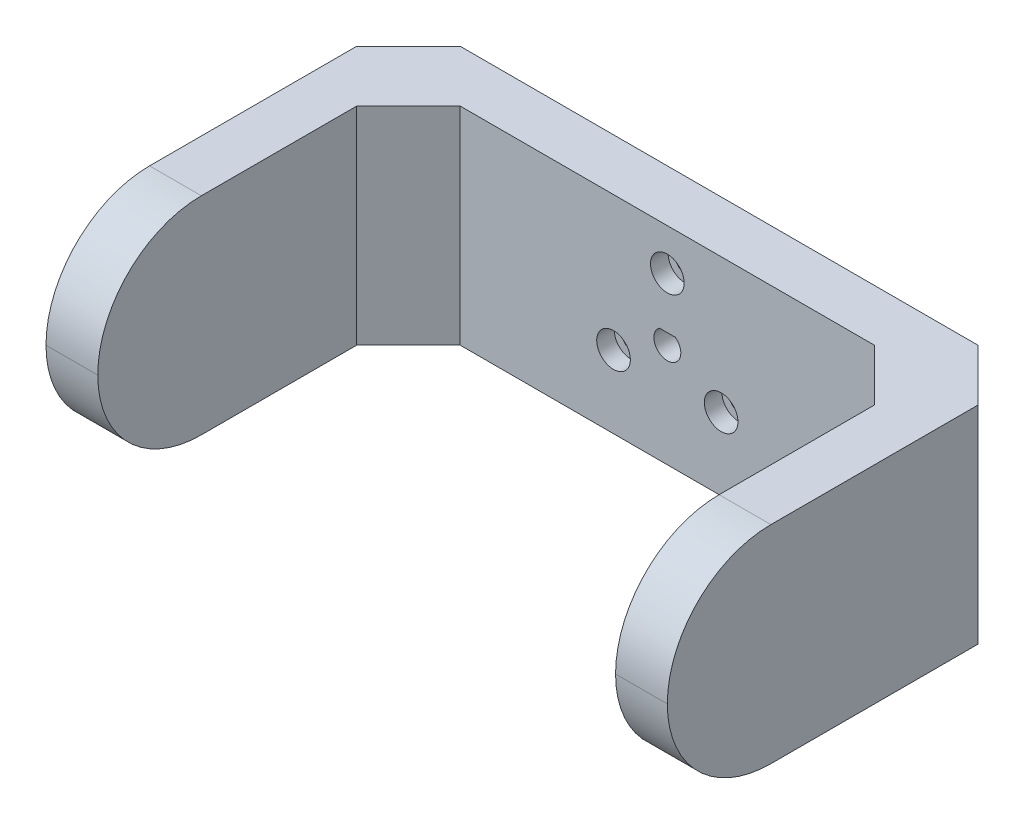
SolidWorks part; units mm, degrees
ref_plane "Ebene vorne" through (0, 0, 0) normal (0, 0, 1) x (1, 0, 0)
ref_plane "Ebene oben" through (0, 0, 0) normal (0, 1, 0) x (1, 0, 0)
ref_plane "Ebene rechts" through (0, 0, 0) normal (1, 0, 0) x (0, 0, -1)
sketch "Skizze1" plane through (0, 0, 0) normal (0, 1, 0) x (1, 0, 0)
  line L0 (-60, 0) -> (60, 0)
  line L5 (0, 0) -> (0, -46.899) construction
  line L6 (-60, 0) -> (-60, -70)
  line L7 (-60, -70) -> (-50, -70)
  line L8 (-50, -70) -> (-50, -10)
  line L9 (-50, -10) -> (50, -10)
  line L10 (50, -10) -> (50, -70)
  line L11 (50, -70) -> (60, -70)
  line L12 (60, -70) -> (60, 0)
  point P4 (0, 0)
  point P8 (-21.7445, -51.9219)
  point P13 (50, 0)
  dimension "D1" = 120
  dimension "D2" = 10
  dimension "D3" = 10
  dimension "D4" = 70
extrude "Aufsatz-Linear austragen1" add sketch "Skizze1" along normal mid plane 40
sketch "Skizze2" plane through (0, 0, 0) normal (0, 0, -1) x (-1, 0, 0)
  line L0 (-1.533, 2.1) -> (1.533, 2.1)
  arc A0 (-1.533, 2.1) -> (1.533, 2.1) centre (0, 0) ccw
  dimension "D1" = 5.2
  dimension "D2" = 4.7
extrude "Schnitt-Linear austragen1" cut sketch "Skizze2" against normal blind 20
chamfer "Fase1" distance 10 angle 45 4 edges at (60, 0, 0) (50, 0, 10) (-60, 0, 0) (-50, 0, 10)
fillet "Verrundung1" radius 20 4 edges at (-55, -20, 70) (-55, 20, 70) (55, 20, 70) (55, -20, 70)
sketch "Skizze3" plane through (0, 0, 10) normal (0, 0, 1) x (1, 0, 0)
  line L0 (0, 0) -> (0, 12) construction
  circle A0 centre (0, 12) radius 3.25
  dimension "D2" = 6.5
  dimension "D1" = 12
extrude "Schnitt-Linear austragen2" cut sketch "Skizze3" against normal blind 3.4
sketch "Skizze4" plane through (0, 0, 6.6) normal (0, 0, 1) x (1, 0, 0)
  circle A0 centre (0, 12) radius 1.7
  dimension "D1" = 3.4
extrude "Schnitt-Linear austragen3" cut sketch "Skizze4" against normal up to surface (6.6 mm away) up to face at (0, -0.25, 0)
pattern_circular "Kreismuster1" count 3 over 360 about axis through (0, 0, 20) along (0, 0, -1) of "Schnitt-Linear austragen3", "Schnitt-Linear austragen2"
